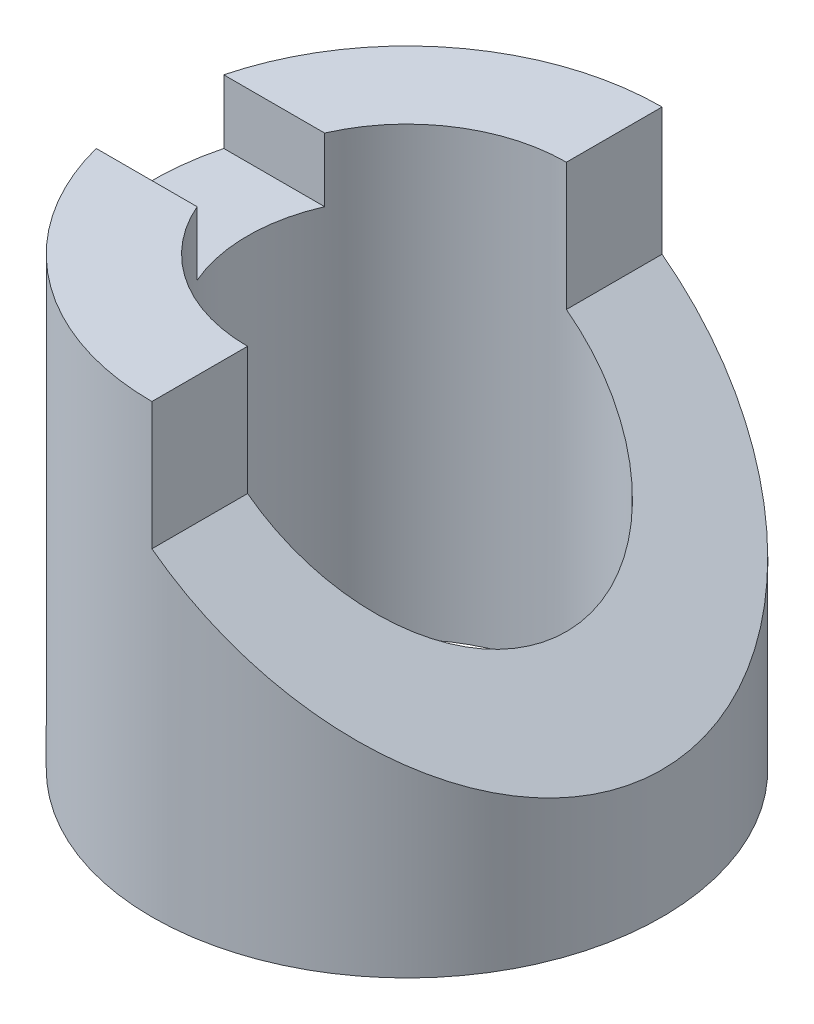
SolidWorks part; units mm, degrees
ref_plane "Front Plane" through (0, 0, 0) normal (0, 0, 1) x (1, 0, 0)
ref_plane "Top Plane" through (0, 0, 0) normal (0, 1, 0) x (1, 0, 0)
ref_plane "Right Plane" through (0, 0, 0) normal (1, 0, 0) x (0, 0, -1)
sketch "Sketch1" plane through (0, 0, 0) normal (0, 1, 0) x (1, 0, 0)
  circle A0 centre (0, 0) radius 25
  circle A1 centre (0, 0) radius 40
  point P3 (0, 0)
  dimension "D1" = 50
  dimension "D2" = 80
extrude "Boss-Extrude1" add sketch "Sketch1" along normal blind 70
sketch "Sketch2" plane through (0, 0, 0) normal (0, 0, 1) x (1, 0, 0)
  line L0 (0, 70) -> (40, 70)
  line L1 (25, 70) -> (-25, 70) construction
  line L2 (0, 70) -> (0, 50)
  line L3 (0, 50) -> (40, 20)
  line L4 (40, 0) -> (40, 70) construction
  line L5 (40, 70) -> (40, 20)
  dimension "D1" = 20
  dimension "D2" = 20
extrude "Cut-Extrude1" cut sketch "Sketch2" against normal blind 70 and the other way blind 70
sketch "Sketch3" plane through (0, 0, 0) normal (1, 0, 0) x (0, 0, -1)
  line L0 (10, 70) -> (10, 60)
  line L1 (40, 70) -> (-40, 70) construction
  line L2 (10, 60) -> (-10, 60)
  line L3 (-10, 60) -> (-10, 70)
  line L4 (-10, 70) -> (10, 70)
  line L5 (10, 70) -> (-10, 70)
  point P6 (0, 60)
  dimension "D1" = 20
  dimension "D2" = 10
extrude "Cut-Extrude2" cut sketch "Sketch3" against normal blind 70 contours L4 L3 L2 L0 region at (0, 65, 0)
